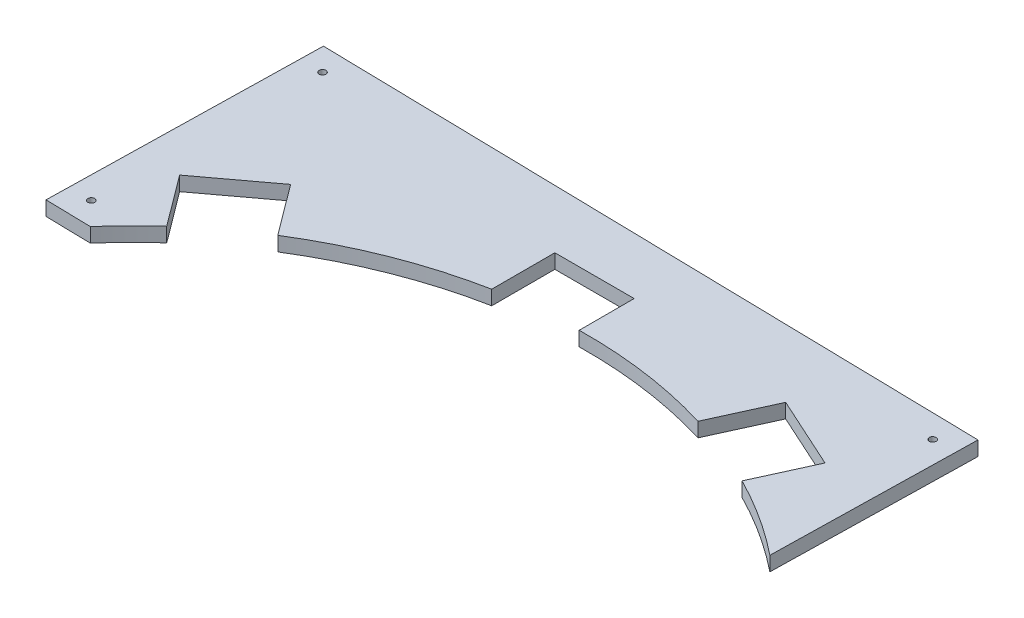
SolidWorks part; units mm, degrees
material "Balsa"
ref_plane "Front Plane" through (0, 0, 0) normal (0, 0, 1) x (1, 0, 0)
ref_plane "Top Plane" through (0, 0, 0) normal (0, 1, 0) x (1, 0, 0)
ref_plane "Right Plane" through (0, 0, 0) normal (1, 0, 0) x (0, 0, -1)
sketch "Sketch1" plane through (0, 0, 0) normal (0, 1, 0) x (1, 0, 0)
  line L0 (-12.8843, 57.5899) -> (-32.8801, 58.0016)
  line L5 (-32.8801, 58.0016) -> (-30.4097, 177.9762)
  line L6 (-30.4097, 177.9762) -> (264.5278, 171.9031)
  line L7 (264.5278, 171.9031) -> (262.6746, 81.9031)
  line L8 (99.6149, 122.2056) -> (99.6149, 150.073)
  line L9 (99.6149, 150.073) -> (134.6149, 150.073)
  line L10 (134.6149, 150.073) -> (134.6149, 125.8222)
  line L11 (195.598, 117.2478) -> (207.7139, 143.8488)
  line L12 (207.7139, 143.8488) -> (239.5656, 129.3413)
  line L13 (239.5656, 129.3413) -> (228.1093, 104.1884)
  line L14 (3.8471, 74.5464) -> (-12.8708, 96.9717)
  line L15 (-12.8708, 96.9717) -> (15.1898, 117.8906)
  line L16 (15.1898, 117.8906) -> (31.8184, 95.5852)
  arc A0 (-12.8843, 57.5899) -> (3.8471, 74.5464) centre (137.592, -74.1557) cw
  arc A1 (31.8184, 95.5852) -> (99.6149, 122.2056) centre (137.592, -74.1557) cw
  arc A2 (134.6149, 125.8222) -> (195.598, 117.2478) centre (137.592, -74.1557) cw
  arc A3 (228.1093, 104.1884) -> (262.6746, 81.9031) centre (137.592, -74.1557) cw
  circle A4 centre (-20.6177, 167.7724) radius 1.5
  circle A5 centre (254.3241, 162.1111) radius 1.5
  circle A6 centre (-22.6763, 67.7936) radius 1.5
  dimension "D5" = 200
  dimension "D11" = 3
  dimension "D14" = 3
  dimension "D17" = 3
  dimension "D1" = 295
  dimension "D2" = 20
  dimension "D3" = 120
  dimension "D4" = 90
  dimension "D6" = 35
  dimension "D7" = 35
  dimension "D8" = 35
  dimension "D9" = 10
  dimension "D10" = 10
  dimension "D12" = 10
  dimension "D13" = 10
  dimension "D15" = 10
  dimension "D16" = 10
extrude "Boss-Extrude1" add sketch "Sketch1" along normal blind 6.35
